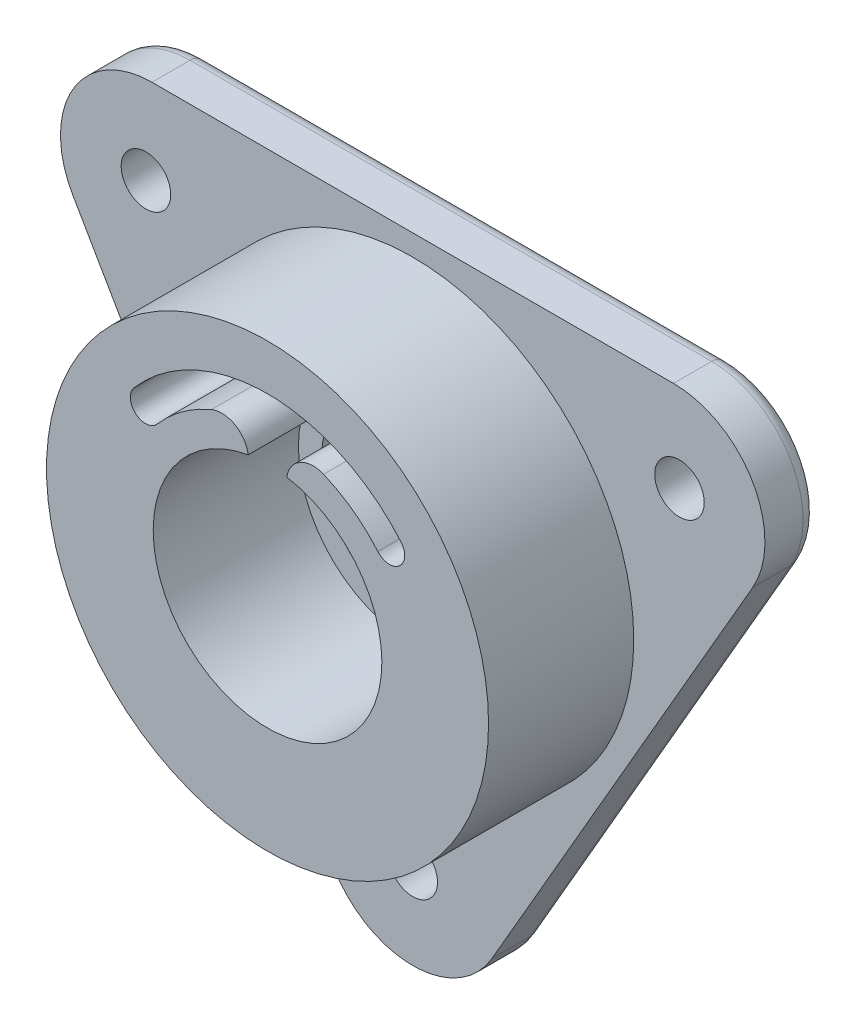
SolidWorks part; units mm, degrees
ref_plane "Plan de face" through (0, 0, 0) normal (0, 0, 1) x (1, 0, 0)
ref_plane "Plan de dessus" through (0, 0, 0) normal (0, 1, 0) x (1, 0, 0)
ref_plane "Plan de droite" through (0, 0, 0) normal (1, 0, 0) x (0, 0, -1)
sketch "Esquisse2" plane through (0, 0, 0) normal (0, 0, 1) x (1, 0, 0)
  circle A0 centre (0, 0) radius 7.5
  circle A1 centre (0, 0) radius 4
  dimension "D1" = 15
  dimension "D2" = 8
sketch "Esquisse1" plane through (0, 0, 0) normal (0, 0, 1) x (1, 0, 0)
  line L0 (-17.5, 10.1036) -> (0, -20.2073) construction
  line L1 (0, -20.2073) -> (17.5, 10.1036) construction
  line L2 (17.5, 10.1036) -> (-17.5, 10.1036) construction
  line L3 (16.0524, 9.2678) -> (-8.4583, -4.8834) construction
  line L4 (0.0575, -0.0332) -> (-30.6383, 17.689) construction
  circle A0 centre (-17.5, 10.1036) radius 1.625
  circle A1 centre (0, -20.2073) radius 1.625
  circle A2 centre (17.5, 10.1036) radius 1.625
  dimension "D2" = 3.25
  dimension "D1" = 35
sketch "Esquisse3" plane through (0, 0, 0) normal (0, 0, 1) x (1, 0, 0)
  line L0 (0, -31.7543) -> (-27.5, 15.8771)
  line L1 (0.0575, -0.0332) -> (-30.6383, 17.689) construction
  line L2 (-27.5, 15.8771) -> (27.5, 15.8771)
  line L3 (16.0524, 9.2678) -> (-8.4583, -4.8834) construction
  line L4 (27.5, 15.8771) -> (0, -31.7543)
  circle A0 centre (-17.5, 10.1036) radius 1.625
  circle A1 centre (17.5, 10.1036) radius 1.625
  circle A2 centre (0, -20.2073) radius 1.625
  circle A3 centre (0, -20.2073) radius 1.625 construction
  circle A4 centre (17.5, 10.1036) radius 1.625 construction
  circle A5 centre (-17.5, 10.1036) radius 1.625 construction
  circle A10 centre (0, 0) radius 6
  circle A13 centre (0, 0) radius 4 construction
  dimension "D2" = 2
  dimension "D1" = 55
extrude "Boss.-Extru.1" add sketch "Esquisse3" along normal blind 3.5
sketch "Esquisse4" plane through (0, 0, 3.5) normal (0, 0, 1) x (1, 0, 0)
  circle A3 centre (0, 0) radius 14.5
  circle A4 centre (0, 0) radius 7.5
  circle A5 centre (0, 0) radius 7.5 construction
  dimension "D1" = 7
extrude "Boss.-Extru.2" add sketch "Esquisse4" along normal blind 9.525
fillet "Congé2" radius 1 3 edges at (0, 15.8771, 0) (-13.75, -7.9386, 0) (13.75, -7.9386, 0)
fillet "Congé3" radius 6 6 edges at (0, -31.1685, 0.2929) (-26.9927, 15.5842, 0.2929) (26.9927, 15.5842, 0.2929) (27.5, 15.8771, 2.25) (-27.5, 15.8771, 2.25) (0, -31.7543, 2.25)
sketch "Esquisse5" plane through (0, 0, 13.025) normal (0, 0, 1) x (1, 0, 0)
  arc A2 (-7.2381, 6.153) -> (7.2381, 6.153) centre (0, 0) cw
  arc A3 (7.2381, 6.153) -> (8.7619, 7.4484) centre (8, 6.8007) ccw
  arc A4 (8.7619, 7.4484) -> (-8.7619, 7.4484) centre (0, 0) ccw
  arc A5 (-8.7619, 7.4484) -> (-7.2381, 6.153) centre (-8, 6.8007) ccw
  circle A6 centre (0, 0) radius 14.5 construction
  circle A7 centre (0, 0) radius 14.5 construction
  circle A8 centre (0, 0) radius 7.5 construction
  point P8 (0, 9.5)
  dimension "D1" = 3
  dimension "D2" = 2
  dimension "D3" = 16
extrude "Enlèv. mat.-Extru.1" cut sketch "Esquisse5" against normal through all
sketch "Esquisse6" plane through (0, 0, 13.025) normal (0, 0, 1) x (1, 0, 0)
  line L0 (-8.0864, 7.1458) -> (8.0864, 7.1458) construction
  arc A0 (-2.3226, 5.5322) -> (-3.6774, 8.7594) centre (-3, 7.1458) ccw
  circle A1 centre (0, 0) radius 6 construction
  arc A2 (7.2381, 6.153) -> (-7.2381, 6.153) centre (0, 0) ccw construction
  arc A3 (3.6774, 8.7594) -> (2.3226, 5.5322) centre (3, 7.1458) ccw
  arc A5 (3.6774, 8.7594) -> (-3.6774, 8.7594) centre (0, 0) ccw
  arc A6 (2.3226, 5.5322) -> (-2.3226, 5.5322) centre (0, 0) ccw
  point P9 (0, 7.1458)
  dimension "D1" = 6
extrude "Enlèv. mat.-Extru.2" cut sketch "Esquisse6" against normal through all
